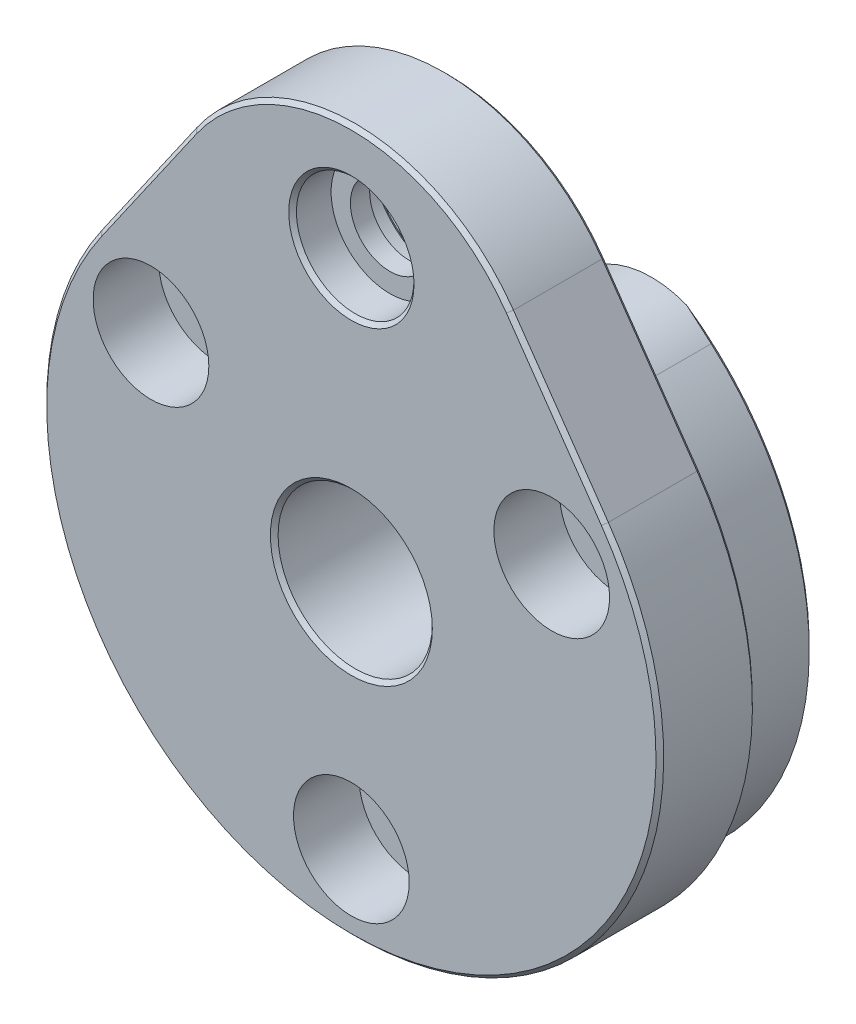
SolidWorks part; units mm, degrees
material "ABS"
ref_plane "前视基准面" through (0, 0, 0) normal (0, 0, 1) x (1, 0, 0)
ref_plane "上视基准面" through (0, 0, 0) normal (0, 1, 0) x (1, 0, 0)
ref_plane "右视基准面" through (0, 0, 0) normal (1, 0, 0) x (0, 0, -1)
other "Configuration Table"
sketch "草图1" plane through (0, 0, 0) normal (0, 0, 1) x (1, 0, 0)
  line L0 (0, 0) -> (0, 15) construction
  line L1 (0, 15) -> (0, 28) construction
  line L2 (0, 28) -> (13.1304, 9.1429)
  line L3 (0, 28) -> (-13.1304, 9.1429)
  line L4 (0, 0) -> (0, -16) construction
  line L5 (10.3923, -6) -> (0, 0) construction
  circle A0 centre (0, 0) radius 16 construction
  circle A1 centre (0, 15) radius 2.05
  arc A2 (-13.1304, 9.1429) -> (13.1304, 9.1429) centre (0, 0) ccw
  circle A3 centre (0, 0) radius 12 construction
  circle A9 centre (0, 0) radius 4
  dimension "D1" = 32
  dimension "D3" = 4.1
  dimension "D5" = 24
  dimension "D9" = 8
  dimension "D2" = 15
  dimension "D4" = 13
  dimension "D7" = 60
extrude "凸台-拉伸1" add sketch "草图1" along normal blind 5
fillet "圆角1" radius 10 1 edges at (0, 28, 2.5)
sketch "草图6" plane through (0, 0, 0) normal (0, 0, -1) x (-1, 0, 0)
  line L0 (0, 0) -> (-10.3923, -6) construction
  line L2 (0, 0) -> (10.3923, -6) construction
  line L3 (0, 0) -> (0, -16) construction
  circle A4 centre (0, 0) radius 4
  arc A5 (-13.1304, 9.1429) -> (13.1304, 9.1429) centre (0, 0) ccw construction
  circle A6 centre (0, 0) radius 14.95
  dimension "D3" = 8
  dimension "D4" = 29.9
  dimension "D5" = 60
  dimension "D6" = 60
  dimension "D7" = 12
  dimension "D8" = 12
extrude "凸台-拉伸2" add sketch "草图6" along normal blind 4
sketch "草图2" plane through (0, 0, 5) normal (0, 0, 1) x (1, 0, 0)
  line L0 (0, 0) -> (0, -16) construction
  arc A0 (-13.1304, 9.1429) -> (13.1304, 9.1429) centre (0, 0) ccw construction
  point P6 (0, -12)
  point P7 (-10.3923, 6)
  point P10 (10.3923, 6)
  dimension "D1" = 12
  dimension "D2" = 3
hole_wizard "M3 六角圆柱头螺钉的柱形沉头孔2" positions "草图2" profile "草图3" counterbore size "M3" standard "GB" end condition up to next
sketch "草图3" plane through (10.3923, 6, 5) normal (1, 0, 0) x (0, -1, 0)
  line L0 (0, 0) -> (0, 9)
  line L1 (0, 9) -> (1.6, 9)
  line L3 (1.6, 9) -> (1.6, 3.4)
  line L4 (1.6, 3.4) -> (3, 3.4)
  line L5 (3, 3.4) -> (3, 0)
  line L7 (3, 0) -> (0, 0)
  line L11 (0, -6.35) -> (0, 107.95) construction
  dimension "通孔孔直径" = 3.2
  dimension "通孔孔深度" = 9
  dimension "柱形沉头孔直径" = 6
  dimension "柱形沉头孔深度" = 3.4
sketch "草图8" plane through (0, 0, -4) normal (0, 0, -1) x (-1, 0, 0)
  circle A0 centre (0.0807, 14.9498) radius 5
  circle A1 centre (0, 0) radius 14.95 construction
  dimension "D1" = 10
extrude "切除-拉伸1" cut sketch "草图8" against normal up to surface (4 mm away) up to face at (0, 1.05, 0)
sketch "草图4" plane through (0, 0, 0) normal (0, 0, -1) x (-1, 0, 0)
  circle A2 centre (0, 15) radius 3.75
  dimension "D1" = 7.5
chamfer "倒角1" distance 0.2 angle 45 11 edges at (0, -16, 0) (-10.6685, 12.6786, 0) (10.6685, 12.6786, 0) (0, 20.5, 0) (0, 20.5, 5) (-10.6685, 12.6786, 5) (10.6685, 12.6786, 5) (0, -16, 5) (4, 0, 5) (-4, 0, -4) (0.0807, -14.9498, -4)
extrude "切除-拉伸2" cut sketch "草图4" against normal blind 2
fillet "圆角2" radius 5 2 edges at (-5.0057, 14.0871, -1.9) (4.8533, 14.1403, -1.9)
chamfer "倒角3" [suppressed] distance 0.5 angle 45
sketch "草图9" plane through (0, 0, -4) normal (0, 0, -1) x (-1, 0, 0)
  line L0 (0, 0) -> (10.3923, -6) construction
  line L1 (0, 0) -> (0, -12) construction
  line L2 (0, 0) -> (-10.3923, -6) construction
  circle A0 centre (0, 0) radius 12 construction
  point P7 (10.3923, -6)
  point P8 (-10.3923, -6)
  dimension "D1" = 24
  dimension "D2" = 60
  dimension "D3" = 60
hole_wizard "Ø3.0mm 暗销孔1" positions "草图9" profile "草图10" hole size "Ø3.0" standard "GB"
sketch "草图10" plane through (10.3923, -6, -4) normal (1, 0, 0) x (0, 1, 0)
  line L0 (0, 0) -> (0, 4.9013)
  line L1 (0, 4.9013) -> (1.5, 4)
  line L2 (1.5, 4) -> (1.5, 0)
  line L5 (1.5, 0) -> (0, 0)
  line L10 (0, 4.9013) -> (-1.5, 4) construction
  line L11 (0, -6.35) -> (0, 107.95) construction
  dimension "孔直径" = 3
  dimension "孔深度" = 4
  dimension "导头角度" = 118
sketch "草图11" plane through (0, 0, 5) normal (0, 0, 1) x (1, 0, 0)
  circle A0 centre (0, 15) radius 3.05
  dimension "D1" = 6.1
extrude "切除-拉伸3" cut sketch "草图11" against normal blind 2
chamfer "倒角4" distance 0.2 angle 45 1 edges at (3.05, 15, 5)
chamfer "倒角5" distance 0.2 angle 45 1 edges at (-3.75, 15, 0)
